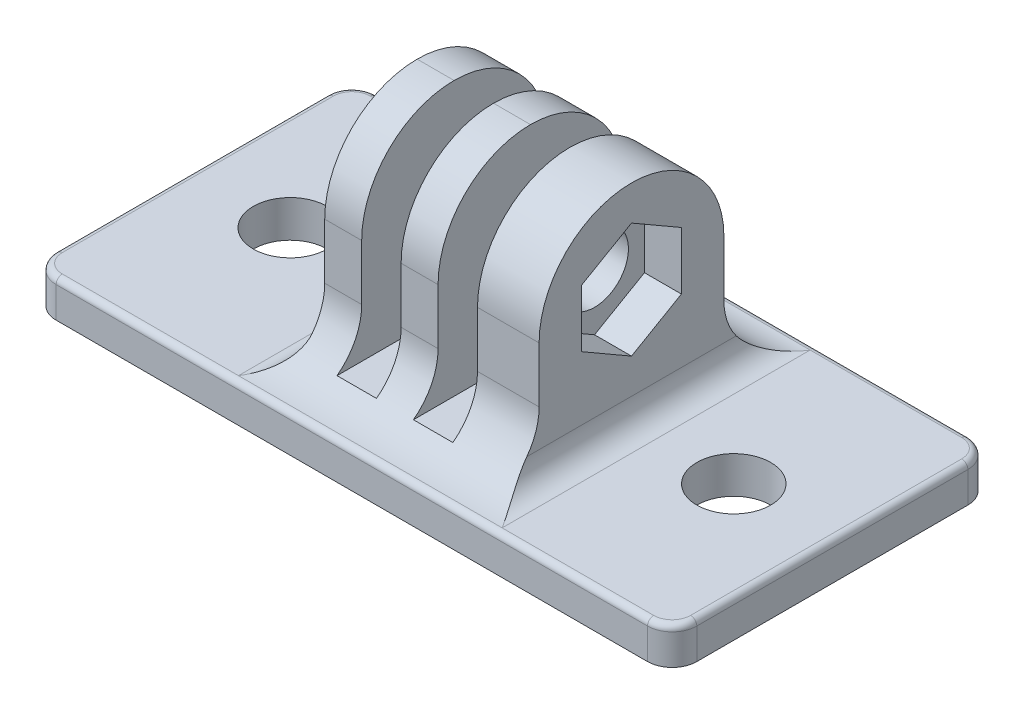
SolidWorks part; units mm, degrees
material "ABS"
ref_plane "Front Plane" through (0, 0, 0) normal (0, 0, 1) x (1, 0, 0)
ref_plane "Top Plane" through (0, 0, 0) normal (0, 1, 0) x (1, 0, 0)
ref_plane "Right Plane" through (0, 0, 0) normal (1, 0, 0) x (0, 0, -1)
sketch "Sketch1" plane through (0, 0, 0) normal (0, 0, 1) x (1, 0, 0)
  line L0 (-7.2, 0) -> (7.2, 0)
  line L1 (7.2, 0) -> (7.2, 17)
  line L2 (7.2, 17) -> (5.2, 17)
  line L3 (5.2, 17) -> (5.2, 1)
  line L4 (5.2, 1) -> (2, 1)
  line L5 (2, 1) -> (2, 17)
  line L6 (2, 17) -> (-1, 17)
  line L7 (-1, 17) -> (-1, 1)
  line L8 (-1, 1) -> (-4.2, 1)
  line L9 (-4.2, 1) -> (-4.2, 17)
  line L10 (-4.2, 17) -> (-7.2, 17)
  line L11 (-7.2, 17) -> (-7.2, 0)
  dimension "D1" = 3
  dimension "D2" = 3.2
  dimension "D3" = 16
  dimension "D4" = 1
  dimension "D5" = 2
extrude "Boss-Extrude1" add sketch "Sketch1" along normal blind 15 contours L7 L8 L9 L10 L11 L0 L1 L2 L3 L4 L5 L6
fillet "Fillet1" radius 7.5 6 edges at (0.5, 17, 15) (6.2, 17, 15) (6.2, 17, 0) (0.5, 17, 0) (-5.7, 17, 0) (-5.7, 17, 15)
sketch "Sketch2" plane through (7.2, 0, 0) normal (1, 0, 0) x (0, 0, -1)
  line L0 (-15, 9.5) -> (-15, 0)
  line L1 (-15, 0) -> (0, 0)
  line L2 (0, 0) -> (0, 9.5)
  line L5 (-7.5, 14.1765) -> (-11.55, 11.8383)
  line L6 (-11.55, 11.8383) -> (-11.55, 7.1617)
  line L7 (-11.55, 7.1617) -> (-7.5, 4.8235)
  line L8 (-7.5, 4.8235) -> (-3.45, 7.1617)
  line L9 (-3.45, 7.1617) -> (-3.45, 11.8383)
  line L10 (-3.45, 11.8383) -> (-7.5, 14.1765)
  arc A0 (0, 9.5) -> (-15, 9.5) centre (-7.5, 9.5) ccw
  circle A1 centre (-7.5, 9.5) radius 4.05 construction
  dimension "D1" = 8.1
extrude "Boss-Extrude2" add sketch "Sketch2" along normal blind 3
hole_wizard "M5 Clearance Hole1" positions "Sketch3" profile "Sketch4" hole size "M5" standard "ANSI Metric" end condition through all
sketch "Sketch3" plane through (10.2, 0, 0) normal (1, 0, 0) x (0, 0, -1)
  point P0 (-7.5, 9.5)
sketch "Sketch4" plane through (10.2, 9.5, 7.5) normal (0, 1, 0) x (0, 0, -1)
  line L0 (0, 0) -> (0, 17.4)
  line L1 (0, 17.4) -> (2.75, 17.4)
  line L2 (2.75, 17.4) -> (2.75, 0)
  line L5 (2.75, 0) -> (0, 0)
  line L11 (0, -6.35) -> (0, 107.95) construction
  dimension "Thru Hole Dia." = 5.5
  dimension "Thru Hole Depth" = 17.4
sketch "Sketch5" plane through (0, 0, 0) normal (0, -1, 0) x (-1, 0, 0)
  line L0 (1, 0) -> (-2, 0) construction
  line L1 (-26.5, 5.5) -> (25.5, 5.5)
  line L2 (-26.5, 5.5) -> (-26.5, -20.5)
  line L3 (-26.5, -20.5) -> (25.5, -20.5)
  line L4 (25.5, 5.5) -> (25.5, -20.5)
  line L5 (-26.5, 5.5) -> (25.5, -20.5) construction
  line L6 (-26.5, -20.5) -> (25.5, 5.5) construction
  line L7 (7.2, -15) -> (7.2, 0) construction
  line L8 (-26.5, -7.5) -> (25.5, -7.5) construction
  line L9 (-0.5, -7.5) -> (-0.5, 5.5) construction
  circle A0 centre (-18.5, -7.5) radius 3
  circle A1 centre (17.5, -7.5) radius 3
  circle A2 centre (-18.5, -7.5) radius 5.2
  circle A3 centre (17.5, -7.5) radius 5.2
  point P0 (-0.5, -7.5)
  point P7 (-0.5, 0)
  point P11 (7.2, -7.5)
  dimension "D3" = 6
  dimension "D4" = 36
  dimension "D5" = 10.4
  dimension "D1" = 26
  dimension "D2" = 52
extrude "Boss-Extrude3" add sketch "Sketch5" along normal blind 3 contours L3 L4 L1 L2 | A0 | A1
fillet "Fillet5" radius 2 4 edges at (26.5, -1.5, -5.5) (26.5, -1.5, 20.5) (-25.5, -1.5, -5.5) (-25.5, -1.5, 20.5) tangent propagation no
fillet "Fillet2" radius 5 2 edges at (1.5, 0, 15) (1.5, 0, 0)
fillet "Fillet3" radius 2 2 edges at (-7.2, 0, 7.5) (10.2, 0, 7.5)
fillet "Fillet6" radius 0.5 8 edges at (-25.5, 0, 7.5) (-24.9142, 0, -4.9142) (0.5, 0, -5.5) (25.9142, 0, -4.9142) (26.5, 0, 7.5) (25.9142, 0, 19.9142) (0.5, 0, 20.5) (-24.9142, 0, 19.9142)
